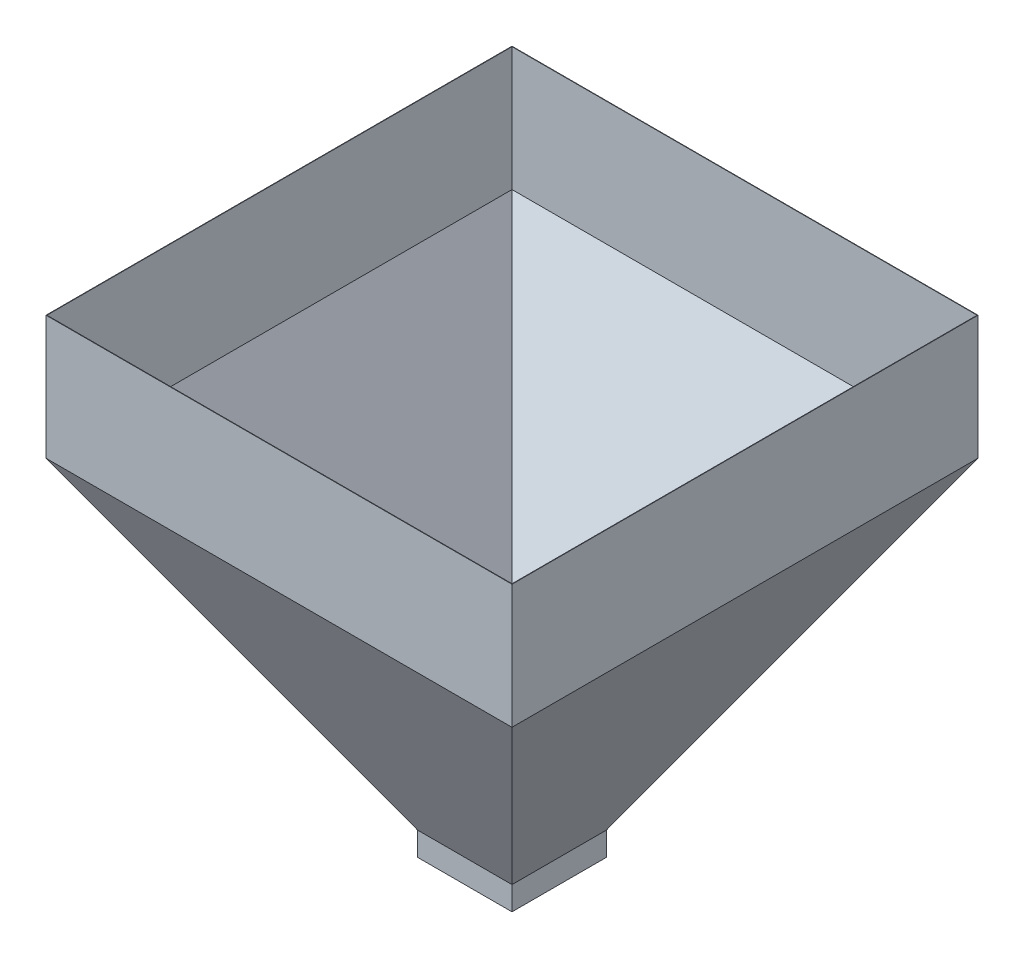
SolidWorks part; units mm, degrees
material "AISI 304"
ref_plane "Alzado" through (0, 0, 0) normal (0, 0, 1) x (1, 0, 0)
ref_plane "Planta" through (0, 0, 0) normal (0, 1, 0) x (1, 0, 0)
ref_plane "Vista lateral" through (0, 0, 0) normal (1, 0, 0) x (0, 0, -1)
sketch "Croquis1" plane through (0, 0, 0) normal (0, 1, 0) x (1, 0, 0)
  line L1 (-395, 395) -> (395, 395)
  line L2 (-395, 395) -> (-395, -395)
  line L3 (-395, -395) -> (395, -395)
  line L4 (395, 395) -> (395, -395)
  line L5 (-395, 395) -> (395, -395) construction
  line L6 (-395, -395) -> (395, 395) construction
  point P0 (0, 0)
  dimension "D1" = 790
ref_plane "Plano1" through (0, -546, 0) normal (0, 1, 0) x (1, 0, 0)
sketch "Croquis2" plane through (0, -546, 0) normal (0, 1, 0) x (1, 0, 0)
  line L0 (-395, 395) -> (395, -395) construction
  line L1 (-80, 80) -> (80, 80)
  line L2 (-80, 80) -> (-80, -80)
  line L3 (-80, -80) -> (80, -80)
  line L4 (80, 80) -> (80, -80)
  line L5 (-80, 80) -> (80, -80) construction
  line L6 (-80, -80) -> (80, 80) construction
  point P0 (0, 0)
  dimension "D1" = 160
loft "Recubrir1" add profiles "Croquis1", "Croquis2" connector at (-395, 0, -395) connector at (-80, -546, -80)
sketch "Croquis3" plane through (0, 0, 0) normal (0, 1, 0) x (1, 0, 0)
  line L1 (-395, 395) -> (395, 395)
  line L2 (-395, 395) -> (-395, -395)
  line L3 (-395, -395) -> (395, -395)
  line L4 (395, 395) -> (395, -395)
extrude "Saliente-Extruir1" add sketch "Croquis3" along normal blind 210
shell "Vaciado2" thickness 0.76 removed face at (0, -546, 0) removed face at (0, 210, 0)
sketch "Croquis5" plane through (0, -546, 0) normal (0, -1, 0) x (1, 0, 0)
  line L1 (-80, 80) -> (80, 80)
  line L2 (-80, 80) -> (-80, -80)
  line L3 (-80, -80) -> (80, -80)
  line L4 (80, 80) -> (80, -80)
  line L5 (-80, 80) -> (80, -80) construction
  line L6 (-80, -80) -> (80, 80) construction
  line L7 (79.1226, -79.1226) -> (-79.1226, -79.1226)
  line L8 (79.1226, -79.1226) -> (79.1226, 79.1226)
  line L9 (79.1226, 79.1226) -> (-79.1226, 79.1226)
  line L10 (-79.1226, -79.1226) -> (-79.1226, 79.1226)
  line L11 (79.1226, -79.1226) -> (-79.1226, 79.1226) construction
  line L12 (79.1226, 79.1226) -> (-79.1226, -79.1226) construction
  point P4 (0, 0)
  point P11 (0, 0)
extrude "Saliente-Extruir2" add sketch "Croquis5" along normal blind 40
